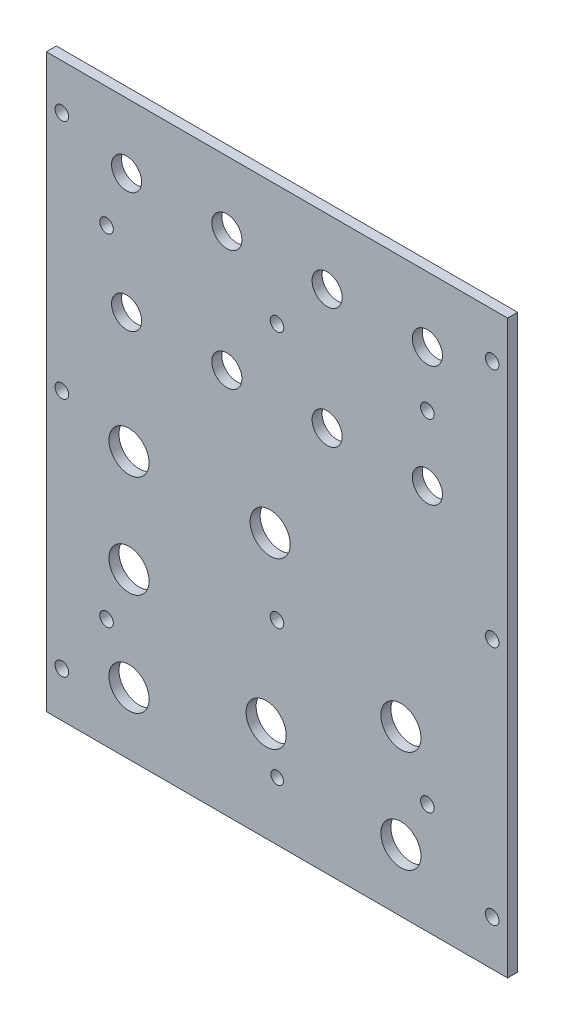
SolidWorks part; units mm, degrees
ref_plane "Front Plane" through (0, 0, 0) normal (0, 0, 1) x (1, 0, 0)
ref_plane "Top Plane" through (0, 0, 0) normal (0, 1, 0) x (1, 0, 0)
ref_plane "Right Plane" through (0, 0, 0) normal (1, 0, 0) x (0, 0, -1)
sketch "Sketch1" plane through (0, 0, 0) normal (0, 0, 1) x (1, 0, 0)
  line L4 (0, 180.975) -> (-146.05, 180.975)
  line L5 (-146.05, 180.975) -> (-146.05, 0)
  line L6 (-146.05, 0) -> (0, 0)
  line L7 (0, 0) -> (0, 180.975)
  line L8 (0, 180.975) -> (-146.05, 180.975)
  line L9 (-146.05, 180.975) -> (-146.05, 0)
  line L10 (-146.05, 0) -> (0, 0)
  line L11 (0, 0) -> (0, 180.975)
  dimension "D1" = 0
extrude "Boss-Extrude1" add sketch "Sketch1" against normal blind 3.175
hole_wizard "#6 Clearance Hole1" positions "Sketch3" profile "Sketch2" hole size "#6" standard "ANSI Inch" end condition through all
sketch "Sketch3" plane through (0, 0, -3.175) normal (0, 0, -1) x (-1, 0, 0)
  point P0 (25.4, 142.875)
  point P7 (73.025, 142.875)
  point P10 (127, 142.875)
  point P13 (25.4, 34.925)
  point P16 (73.025, 61.647)
  point P19 (127, 34.925)
  point P22 (4.8895, 14.2875)
  point P25 (141.1605, 14.2875)
  point P28 (4.8895, 90.4875)
  point P31 (141.1605, 90.4875)
  point P34 (141.1605, 166.6875)
  point P37 (4.8895, 166.6875)
sketch "Sketch2" plane through (-25.4, 142.875, -3.175) normal (1, 0, 0) x (0, 1, 0)
  line L0 (0, 0) -> (0, 3.175)
  line L1 (0, 3.175) -> (2.1526, 3.175)
  line L2 (2.1526, 3.175) -> (2.1526, 0)
  line L5 (2.1526, 0) -> (0, 0)
  line L11 (0, -6.35) -> (0, 107.95) construction
  dimension "Thru Hole Dia." = 4.3053
  dimension "Thru Hole Depth" = 3.175
hole_wizard "3/8 (0.375) Diameter Hole1" positions "Sketch5" profile "Sketch4" hole size "3/8" standard "ANSI Inch" end condition through all
sketch "Sketch5" plane through (0, 0, -3.175) normal (0, 0, -1) x (-1, 0, 0)
  point P0 (25.4, 160.3248)
  point P3 (57.15, 160.3248)
  point P6 (88.9, 160.3248)
  point P9 (120.65, 160.3248)
  point P12 (25.4, 122.2248)
  point P15 (57.15, 122.2248)
  point P18 (88.9, 122.2248)
  point P21 (120.65, 122.2248)
sketch "Sketch4" plane through (-25.4, 160.3248, -3.175) normal (1, 0, 0) x (0, 1, 0)
  line L0 (0, 0) -> (0, 3.175)
  line L1 (0, 3.175) -> (4.7625, 3.175)
  line L2 (4.7625, 3.175) -> (4.7625, 0)
  line L5 (4.7625, 0) -> (0, 0)
  line L11 (0, -6.35) -> (0, 107.95) construction
  dimension "Thru Hole Dia." = 9.525
  dimension "Thru Hole Depth" = 3.175
hole_wizard "1/2 (0.5) Diameter Hole1" positions "Sketch7" profile "Sketch6" hole size "1/2" standard "ANSI Inch" end condition through all
sketch "Sketch7" plane through (0, 0, -3.175) normal (0, 0, -1) x (-1, 0, 0)
  point P0 (75.184, 84.455)
  point P3 (119.888, 84.455)
  point P6 (119.888, 52.07)
  point P9 (33.782, 52.07)
  point P12 (33.782, 19.685)
  point P15 (119.888, 19.685)
  point P18 (76.454, 31.496)
sketch "Sketch6" plane through (-75.184, 84.455, -3.175) normal (1, 0, 0) x (0, 1, 0)
  line L0 (0, 0) -> (0, 3.175)
  line L1 (0, 3.175) -> (6.35, 3.175)
  line L2 (6.35, 3.175) -> (6.35, 0)
  line L5 (6.35, 0) -> (0, 0)
  line L11 (0, -6.35) -> (0, 107.95) construction
  dimension "Thru Hole Dia." = 12.7
  dimension "Thru Hole Depth" = 3.175
hole_wizard "5/32 (0.15625) Diameter Hole1" positions "Sketch9" profile "Sketch8" hole size "5/32" standard "ANSI Inch" end condition through all
sketch "Sketch9" plane through (0, 0, -3.175) normal (0, 0, -1) x (-1, 0, 0)
  point P0 (72.9632, 18.4682)
sketch "Sketch8" plane through (-72.9632, 18.4682, -3.175) normal (1, 0, 0) x (0, 1, 0)
  line L0 (0, 0) -> (0, 3.175)
  line L1 (0, 3.175) -> (1.9844, 3.175)
  line L2 (1.9844, 3.175) -> (1.9844, 0)
  line L5 (1.9844, 0) -> (0, 0)
  line L11 (0, -6.35) -> (0, 107.95) construction
  dimension "Thru Hole Dia." = 3.9688
  dimension "Thru Hole Depth" = 3.175
